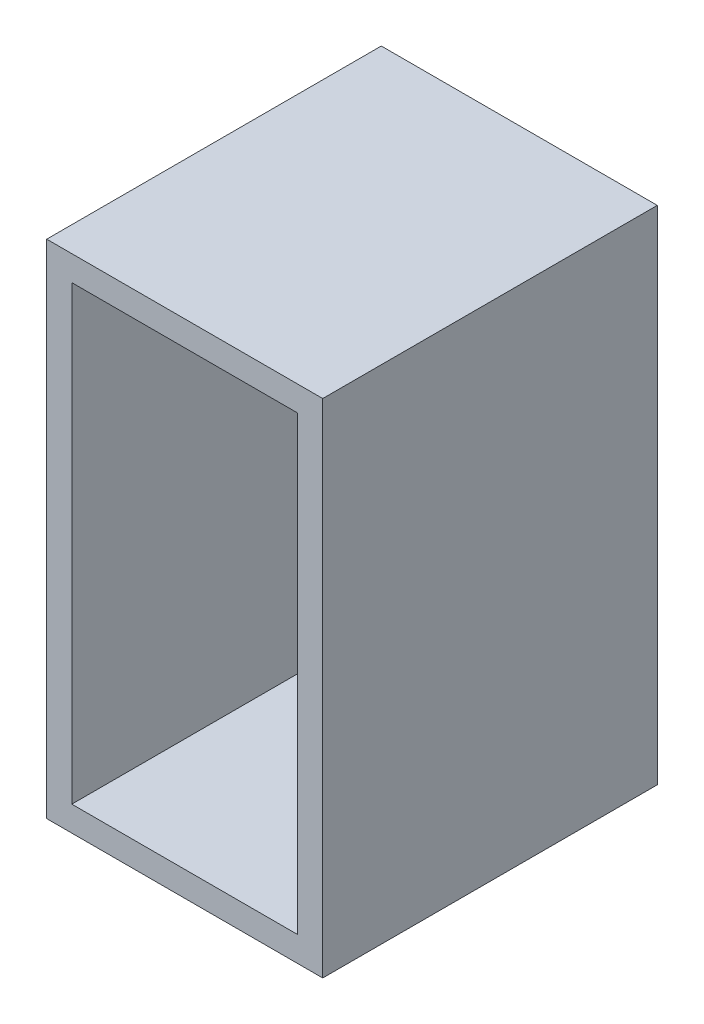
SolidWorks part; units mm, degrees
ref_plane "정면" through (0, 0, 0) normal (0, 0, 1) x (1, 0, 0)
ref_plane "윗면" through (0, 0, 0) normal (0, 1, 0) x (1, 0, 0)
ref_plane "우측면" through (0, 0, 0) normal (1, 0, 0) x (0, 0, -1)
sketch "스케치1" plane through (0, 0, 0) normal (0, 0, 1) x (1, 0, 0)
  line L1 (0, 0) -> (16.5, 0)
  line L2 (0, 0) -> (0, -30)
  line L3 (0, -30) -> (16.5, -30)
  line L4 (16.5, 0) -> (16.5, -30)
  line L5 (3, -3) -> (13.5, -3)
  line L6 (3, -3) -> (3, -8.5)
  line L7 (3, -8.5) -> (13.5, -8.5)
  line L8 (13.5, -3) -> (13.5, -8.5)
  line L9 (1.5, -1.5) -> (15, -1.5)
  line L10 (1.5, -1.5) -> (1.5, -28.5)
  line L11 (1.5, -28.5) -> (15, -28.5)
  line L12 (15, -1.5) -> (15, -28.5)
  dimension "D1" = 3
  dimension "D2" = 10.5
  dimension "D3" = 5.5
  dimension "D4" = 3
  dimension "D5" = 3
  dimension "D6" = 30
  dimension "D7" = 1.5
  dimension "D8" = 1.5
  dimension "D9" = 1.5
  dimension "D10" = 1.5
extrude "보스-돌출1" add sketch "스케치1" along normal blind 1.5 contours L12 L9 L10 L11 L5 L8 L7 L6 region at (8.25, -16.7414, 0)
extrude "보스-돌출2" add sketch "스케치1<3>" along normal blind 20 contours L4 L1 L2 L3 L9 L12 L11 L10 region at (8.25, -0.3424, 0)
sketch "스케치1<3>" plane through (0, 0, 0) normal (0, 0, 1) x (1, 0, 0) same geometry as "스케치1"
sketch "스케치3" plane through (0, 0, 20) normal (0, 0, 1) x (1, 0, 0)
  line L0 (16.5, 0) -> (16.5, -30) construction
  line L1 (0, 0) -> (16.5, 0)
  line L2 (0, 0) -> (0, -13.2385)
  line L3 (0, -13.2385) -> (16.5, -13.2385)
  line L4 (16.5, 0) -> (16.5, -13.2385)
